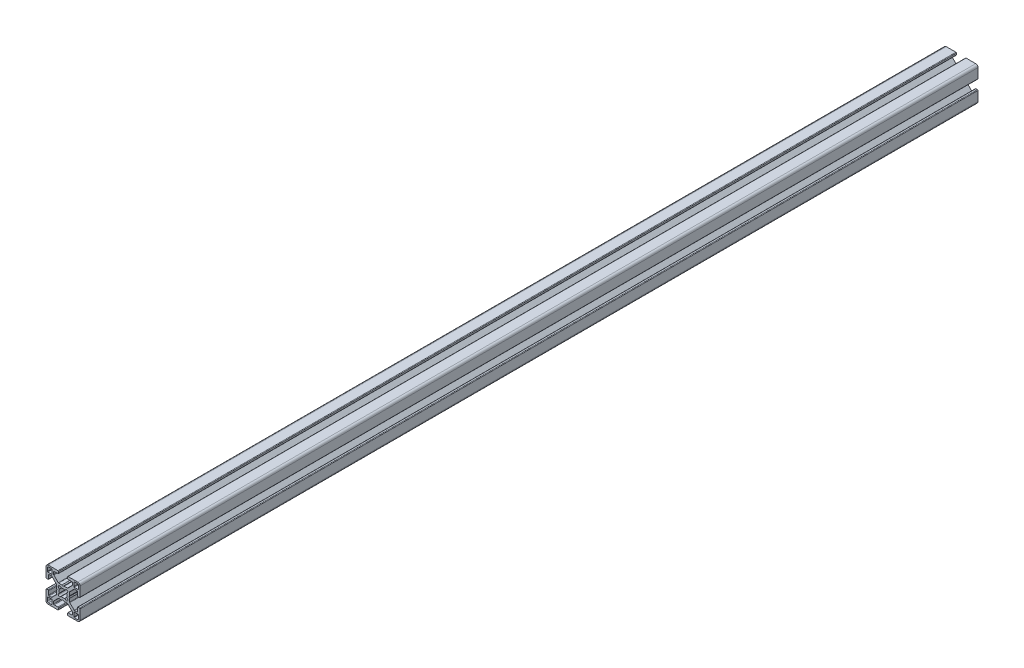
SolidWorks part; units mm, degrees
ref_plane "Plano frontal" through (0, 0, 0) normal (0, 0, 1) x (1, 0, 0)
ref_plane "Plano superior" through (0, 0, 0) normal (0, 1, 0) x (1, 0, 0)
ref_plane "Plano direito" through (0, 0, 0) normal (1, 0, 0) x (0, 0, -1)
ref_plane "Plano1"
sketch "Esboço1" plane through (0, 0, 0) normal (0, 0, 1) x (1, 0, 0)
  line L0 (-13, -15) -> (-4.508, -15)
  line L1 (-4, -14.492) -> (-4, -13.251)
  line L2 (-4.508, -12.743) -> (-7.742, -12.743)
  line L3 (-8.25, -12.235) -> (-8.25, -10.2642)
  line L4 (-8.1012, -9.905) -> (-4.1795, -5.9833)
  line L5 (-3.8203, -5.8345) -> (-0.949, -5.8345)
  line L6 (-0.949, -5.8345) -> (0, -5.325)
  line L7 (0, -5.325) -> (0.949, -5.8345)
  line L8 (0.949, -5.8345) -> (3.8216, -5.8345)
  line L9 (4.1808, -5.9833) -> (8.1012, -9.9037)
  line L10 (8.25, -10.2629) -> (8.25, -12.235)
  line L11 (7.742, -12.743) -> (4.508, -12.743)
  line L12 (4, -13.251) -> (4, -14.492)
  line L13 (4.508, -15) -> (13, -15)
  line L14 (15, -13) -> (15, -4.508)
  line L15 (14.492, -4) -> (13.251, -4)
  line L16 (12.743, -4.508) -> (12.743, -7.742)
  line L17 (12.235, -8.25) -> (10.2642, -8.25)
  line L18 (9.905, -8.1012) -> (5.9833, -4.1795)
  line L19 (5.8345, -3.8203) -> (5.8345, -0.949)
  line L20 (5.8345, -0.949) -> (5.325, 0)
  line L21 (5.325, 0) -> (5.8345, 0.949)
  line L22 (5.8345, 0.949) -> (5.8345, 3.8216)
  line L23 (5.9833, 4.1808) -> (9.9037, 8.1012)
  line L24 (10.2629, 8.25) -> (12.235, 8.25)
  line L25 (12.743, 7.742) -> (12.743, 4.508)
  line L26 (13.251, 4) -> (14.492, 4)
  line L27 (15, 4.508) -> (15, 13)
  line L28 (13, 15) -> (4.508, 15)
  line L29 (4, 14.492) -> (4, 13.251)
  line L30 (4.508, 12.743) -> (7.742, 12.743)
  line L31 (8.25, 12.235) -> (8.25, 10.2642)
  line L32 (8.1012, 9.905) -> (4.1795, 5.9833)
  line L33 (3.8203, 5.8345) -> (0.949, 5.8345)
  line L34 (0.949, 5.8345) -> (0, 5.325)
  line L35 (0, 5.325) -> (-0.949, 5.8345)
  line L36 (-0.949, 5.8345) -> (-3.8216, 5.8345)
  line L37 (-4.1808, 5.9833) -> (-8.1012, 9.9037)
  line L38 (-8.25, 10.2629) -> (-8.25, 12.235)
  line L39 (-7.742, 12.743) -> (-4.508, 12.743)
  line L40 (-4, 13.251) -> (-4, 14.492)
  line L41 (-4.508, 15) -> (-13, 15)
  line L42 (-15, 13) -> (-15, 4.508)
  line L43 (-14.492, 4) -> (-13.251, 4)
  line L44 (-12.743, 4.508) -> (-12.743, 7.742)
  line L45 (-12.235, 8.25) -> (-10.2642, 8.25)
  line L46 (-9.905, 8.1012) -> (-5.9833, 4.1795)
  line L47 (-5.8345, 3.8203) -> (-5.8345, 0.949)
  line L48 (-5.8345, 0.949) -> (-5.325, 0)
  line L49 (-5.325, 0) -> (-5.8345, -0.949)
  line L50 (-5.8345, -0.949) -> (-5.8345, -3.8216)
  line L51 (-5.9833, -4.1808) -> (-9.9037, -8.1012)
  line L52 (-10.2629, -8.25) -> (-12.235, -8.25)
  line L53 (-12.743, -7.742) -> (-12.743, -4.508)
  line L54 (-13.251, -4) -> (-14.492, -4)
  line L55 (-15, -4.508) -> (-15, -13)
  line L56 (9.5, 13.319) -> (9.5, 9.881)
  line L57 (9.881, 9.5) -> (13.319, 9.5)
  line L58 (13.7, 9.881) -> (13.7, 12.7)
  line L59 (12.7, 13.7) -> (9.881, 13.7)
  line L60 (9.5, -9.881) -> (9.5, -13.319)
  line L61 (9.881, -13.7) -> (12.7, -13.7)
  line L62 (13.7, -12.7) -> (13.7, -9.881)
  line L63 (13.319, -9.5) -> (9.881, -9.5)
  line L64 (-13.7, -9.881) -> (-13.7, -12.7)
  line L65 (-12.7, -13.7) -> (-9.881, -13.7)
  line L66 (-9.5, -13.319) -> (-9.5, -9.881)
  line L67 (-9.881, -9.5) -> (-13.319, -9.5)
  line L68 (-13.7, 12.7) -> (-13.7, 9.881)
  line L69 (-13.319, 9.5) -> (-9.881, 9.5)
  line L70 (-9.5, 9.881) -> (-9.5, 13.319)
  line L71 (-9.881, 13.7) -> (-12.7, 13.7)
  line L72 (-4.0107, 2.5139) -> (-3.1982, 1.4942)
  line L73 (-3.1982, -1.4942) -> (-4.0107, -2.5139)
  line L74 (-2.5139, -4.0107) -> (-1.4942, -3.1982)
  line L75 (1.4942, -3.1982) -> (2.5139, -4.0107)
  line L76 (4.0107, -2.5139) -> (3.1982, -1.4942)
  line L77 (3.1982, 1.4942) -> (4.0107, 2.5139)
  line L78 (2.5139, 4.0107) -> (1.4942, 3.1982)
  line L79 (-1.4942, 3.1982) -> (-2.5139, 4.0107)
  arc A0 (-15, -13) -> (-13, -15) centre (-13, -13) ccw
  arc A1 (-4.508, -15) -> (-4, -14.492) centre (-4.508, -14.492) ccw
  arc A2 (-4, -13.251) -> (-4.508, -12.743) centre (-4.508, -13.251) ccw
  arc A3 (-8.25, -12.235) -> (-7.742, -12.743) centre (-7.742, -12.235) ccw
  arc A4 (-8.1012, -9.905) -> (-8.25, -10.2642) centre (-7.742, -10.2642) ccw
  arc A5 (-3.8203, -5.8345) -> (-4.1795, -5.9833) centre (-3.8203, -6.3425) ccw
  arc A6 (4.1808, -5.9833) -> (3.8216, -5.8345) centre (3.8216, -6.3425) ccw
  arc A7 (8.25, -10.2629) -> (8.1012, -9.9037) centre (7.742, -10.2629) ccw
  arc A8 (7.742, -12.743) -> (8.25, -12.235) centre (7.742, -12.235) ccw
  arc A9 (4.508, -12.743) -> (4, -13.251) centre (4.508, -13.251) ccw
  arc A10 (4, -14.492) -> (4.508, -15) centre (4.508, -14.492) ccw
  arc A11 (13, -15) -> (15, -13) centre (13, -13) ccw
  arc A12 (15, -4.508) -> (14.492, -4) centre (14.492, -4.508) ccw
  arc A13 (13.251, -4) -> (12.743, -4.508) centre (13.251, -4.508) ccw
  arc A14 (12.235, -8.25) -> (12.743, -7.742) centre (12.235, -7.742) ccw
  arc A15 (9.905, -8.1012) -> (10.2642, -8.25) centre (10.2642, -7.742) ccw
  arc A16 (5.8345, -3.8203) -> (5.9833, -4.1795) centre (6.3425, -3.8203) ccw
  arc A17 (5.9833, 4.1808) -> (5.8345, 3.8216) centre (6.3425, 3.8216) ccw
  arc A18 (10.2629, 8.25) -> (9.9037, 8.1012) centre (10.2629, 7.742) ccw
  arc A19 (12.743, 7.742) -> (12.235, 8.25) centre (12.235, 7.742) ccw
  arc A20 (12.743, 4.508) -> (13.251, 4) centre (13.251, 4.508) ccw
  arc A21 (14.492, 4) -> (15, 4.508) centre (14.492, 4.508) ccw
  arc A22 (15, 13) -> (13, 15) centre (13, 13) ccw
  arc A23 (4.508, 15) -> (4, 14.492) centre (4.508, 14.492) ccw
  arc A24 (4, 13.251) -> (4.508, 12.743) centre (4.508, 13.251) ccw
  arc A25 (8.25, 12.235) -> (7.742, 12.743) centre (7.742, 12.235) ccw
  arc A26 (8.1012, 9.905) -> (8.25, 10.2642) centre (7.742, 10.2642) ccw
  arc A27 (3.8203, 5.8345) -> (4.1795, 5.9833) centre (3.8203, 6.3425) ccw
  arc A28 (-4.1808, 5.9833) -> (-3.8216, 5.8345) centre (-3.8216, 6.3425) ccw
  arc A29 (-8.25, 10.2629) -> (-8.1012, 9.9037) centre (-7.742, 10.2629) ccw
  arc A30 (-7.742, 12.743) -> (-8.25, 12.235) centre (-7.742, 12.235) ccw
  arc A31 (-4.508, 12.743) -> (-4, 13.251) centre (-4.508, 13.251) ccw
  arc A32 (-4, 14.492) -> (-4.508, 15) centre (-4.508, 14.492) ccw
  arc A33 (-13, 15) -> (-15, 13) centre (-13, 13) ccw
  arc A34 (-15, 4.508) -> (-14.492, 4) centre (-14.492, 4.508) ccw
  arc A35 (-13.251, 4) -> (-12.743, 4.508) centre (-13.251, 4.508) ccw
  arc A36 (-12.235, 8.25) -> (-12.743, 7.742) centre (-12.235, 7.742) ccw
  arc A37 (-9.905, 8.1012) -> (-10.2642, 8.25) centre (-10.2642, 7.742) ccw
  arc A38 (-5.8345, 3.8203) -> (-5.9833, 4.1795) centre (-6.3425, 3.8203) ccw
  arc A39 (-5.9833, -4.1808) -> (-5.8345, -3.8216) centre (-6.3425, -3.8216) ccw
  arc A40 (-10.2629, -8.25) -> (-9.9037, -8.1012) centre (-10.2629, -7.742) ccw
  arc A41 (-12.743, -7.742) -> (-12.235, -8.25) centre (-12.235, -7.742) ccw
  arc A42 (-12.743, -4.508) -> (-13.251, -4) centre (-13.251, -4.508) ccw
  arc A43 (-14.492, -4) -> (-15, -4.508) centre (-14.492, -4.508) ccw
  arc A44 (9.5, 9.881) -> (9.881, 9.5) centre (9.881, 9.881) ccw
  arc A45 (13.319, 9.5) -> (13.7, 9.881) centre (13.319, 9.881) ccw
  arc A46 (13.7, 12.7) -> (12.7, 13.7) centre (12.7, 12.7) ccw
  arc A47 (9.881, 13.7) -> (9.5, 13.319) centre (9.881, 13.319) ccw
  arc A48 (9.5, -13.319) -> (9.881, -13.7) centre (9.881, -13.319) ccw
  arc A49 (12.7, -13.7) -> (13.7, -12.7) centre (12.7, -12.7) ccw
  arc A50 (13.7, -9.881) -> (13.319, -9.5) centre (13.319, -9.881) ccw
  arc A51 (9.881, -9.5) -> (9.5, -9.881) centre (9.881, -9.881) ccw
  arc A52 (-13.7, -12.7) -> (-12.7, -13.7) centre (-12.7, -12.7) ccw
  arc A53 (-9.881, -13.7) -> (-9.5, -13.319) centre (-9.881, -13.319) ccw
  arc A54 (-9.5, -9.881) -> (-9.881, -9.5) centre (-9.881, -9.881) ccw
  arc A55 (-13.319, -9.5) -> (-13.7, -9.881) centre (-13.319, -9.881) ccw
  arc A56 (-13.7, 9.881) -> (-13.319, 9.5) centre (-13.319, 9.881) ccw
  arc A57 (-9.881, 9.5) -> (-9.5, 9.881) centre (-9.881, 9.881) ccw
  arc A58 (-9.5, 13.319) -> (-9.881, 13.7) centre (-9.881, 13.319) ccw
  arc A59 (-12.7, 13.7) -> (-13.7, 12.7) centre (-12.7, 12.7) ccw
  arc A60 (-2.5139, 4.0107) -> (-4.0107, 2.5139) centre (-3.142, 3.142) ccw
  arc A61 (-3.1982, 1.4942) -> (-3.1982, -1.4942) centre (0, 0) ccw
  arc A62 (-4.0107, -2.5139) -> (-2.5139, -4.0107) centre (-3.142, -3.142) ccw
  arc A63 (-1.4942, -3.1982) -> (1.4942, -3.1982) centre (0, 0) ccw
  arc A64 (2.5139, -4.0107) -> (4.0107, -2.5139) centre (3.142, -3.142) ccw
  arc A65 (3.1982, -1.4942) -> (3.1982, 1.4942) centre (0, 0) ccw
  arc A66 (4.0107, 2.5139) -> (2.5139, 4.0107) centre (3.142, 3.142) ccw
  arc A67 (1.4942, 3.1982) -> (-1.4942, 3.1982) centre (0, 0) ccw
extrude "Extrusion1" add sketch "Esboço1" against normal blind 792 contours L54 A43 L55 A0 L0 A1 L1 A2 L2 A3 L3 A4 L4 A5 L5 L6 L7 L8 A6 L9 A7 L10 A8 L11 A9 L12 A10 L13 A11 L14 A12 L15 A13 L16 A14 L17 A15 L18 A16 L19 L20 L21 L22 A17 L23 A18 L24 A19 L25 A20 L26 region at (-14.1142, -14.1142, 0)
